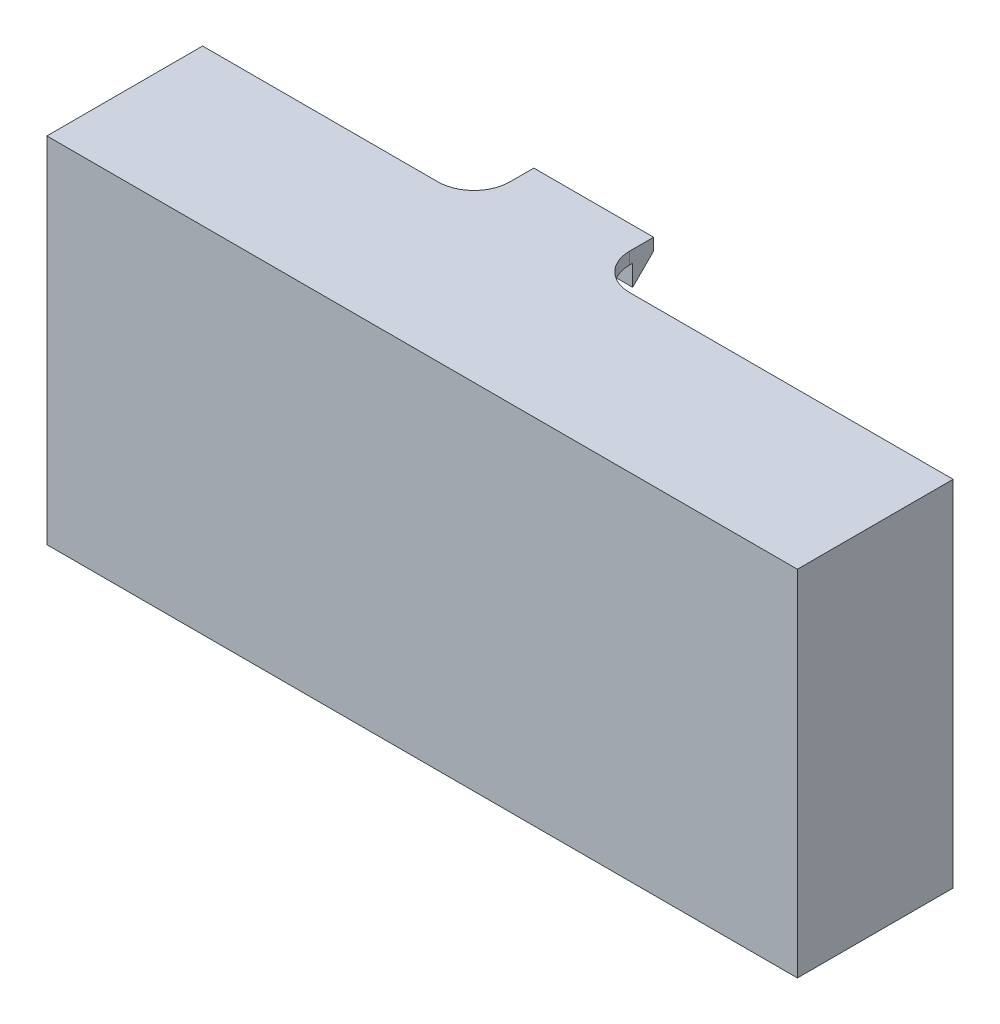
SolidWorks part; units mm, degrees
note: The reader was unsure of these and kept them because the rebuilt part matched: shared geometry of "Sketch13<2>".
ref_plane "Front Plane" through (0, 0, 0) normal (0, 0, 1) x (1, 0, 0)
ref_plane "Top Plane" through (0, 0, 0) normal (0, 1, 0) x (1, 0, 0)
ref_plane "Right Plane" through (0, 0, 0) normal (1, 0, 0) x (0, 0, -1)
sketch "Sketch1" plane through (0, 0, 0) normal (0, 0, 1) x (1, 0, 0)
  line L5 (1.25, -1.25) -> (1.25, 28.301)
  line L6 (1.25, 28.301) -> (-61.3972, 28.301)
  line L7 (-61.3972, 28.301) -> (-61.3972, -1.25)
  line L8 (-61.3972, -1.25) -> (1.25, -1.25)
  line L13 (0.25, -0.25) -> (0.25, 27.301)
  line L14 (0.25, 27.301) -> (-60.3972, 27.301)
  line L15 (-60.3972, 27.301) -> (-60.3972, -0.25)
  line L16 (-60.3972, -0.25) -> (0.25, -0.25)
  dimension "D2" = 1
extrude "Boss-Extrude1" add sketch "Sketch1" along normal blind 11
sketch "Sketch3" plane through (-61.3972, 0, 0) normal (-1, 0, 0) x (0, 0, 1)
  line L0 (0, 17.5514) -> (0.75, 18.3233)
  line L1 (0, 28.301) -> (0, -1.25) construction
  line L2 (0.75, 18.3233) -> (0.75, 24.3233)
  line L3 (0.75, 24.3233) -> (0, 25.0952)
  line L4 (0, 25.0952) -> (0, 17.5514)
  line L5 (0, 21.3233) -> (11, 21.3233) construction
  line L6 (11, 28.301) -> (11, -1.25) construction
  line L7 (-2.8448, 17.5514) -> (0, 17.5514) construction
  point P11 (0.75, 21.3233)
  dimension "D1" = 6
  dimension "D2" = 0.75
extrude "Cut-Extrude1" cut sketch "Sketch3" against normal up to next
sketch "Sketch4" plane through (0, -0.25, 0) normal (0, 1, 0) x (1, 0, 0)
  line L0 (0, -1.5875) -> (-60.1472, -1.5875) construction
  line L1 (-55.3972, -1.8375) -> (-53.3972, -1.8375)
  line L2 (-55.3972, -1.8375) -> (-55.3972, -2.8375)
  line L3 (-55.3972, -2.8375) -> (-53.3972, -2.8375)
  line L4 (-53.3972, -1.8375) -> (-53.3972, -2.8375)
  line L5 (-60.3972, -11) -> (-60.3972, 0) construction
  line L6 (-6.75, -1.8375) -> (-4.75, -1.8375)
  line L7 (-6.75, -1.8375) -> (-6.75, -2.8375)
  line L8 (-6.75, -2.8375) -> (-4.75, -2.8375)
  line L9 (-4.75, -1.8375) -> (-4.75, -2.8375)
  line L10 (0.25, -11) -> (0.25, 0) construction
  point P10 (-55.3972, -2.3375)
  dimension "D1" = 2
  dimension "D2" = 1
  dimension "D3" = 5
  dimension "D4" = 5
  dimension "D5" = 0.25
extrude "Boss-Extrude2" add sketch "Sketch4" along normal blind 1
sketch "Sketch6" plane through (0, 27.301, 0) normal (0, -1, 0) x (1, 0, 0)
  line L1 (-1.75, 1.8375) -> (-3.75, 1.8375)
  line L2 (-1.75, 1.8375) -> (-1.75, 2.8375)
  line L3 (-1.75, 2.8375) -> (-3.75, 2.8375)
  line L4 (-3.75, 1.8375) -> (-3.75, 2.8375)
  line L5 (-49.3776, 1.5875) -> (-49.3776, 6.2611) construction
  line L6 (-50.3776, 2.2832) -> (-52.3776, 2.2832)
  line L7 (-50.3776, 2.2832) -> (-50.3776, 3.2832)
  line L8 (-50.3776, 3.2832) -> (-52.3776, 3.2832)
  line L9 (-52.3776, 2.2832) -> (-52.3776, 3.2832)
  line L10 (0.25, 11) -> (0.25, 0) construction
  line L11 (-60.1472, 1.5875) -> (0, 1.5875) construction
  dimension "D1" = 1
  dimension "D2" = 2
  dimension "D3" = 1
  dimension "D4" = 2
  dimension "D5" = 0.25
extrude "Boss-Extrude3" add sketch "Sketch6" along normal blind 1
sketch "Sketch7" plane through (1.25, 0, 0) normal (1, 0, 0) x (0, 0, -1)
  line L1 (0, 27.951) -> (1, 27.951)
  line L3 (0, 27.301) -> (0, 25.0952) construction
  line L4 (0, 26.951) -> (0, 27.951)
  line L5 (0, 27.051) -> (-1.5875, 27.051) construction
  line L6 (1, 27.951) -> (1, 26.951)
  line L7 (1, 26.951) -> (0, 26.951)
  dimension "D1" = 1
  dimension "D2" = 1
  dimension "D3" = 0.1
extrude "Boss-Extrude4" add sketch "Sketch7" against normal blind 10 from offset 30 contours L4 L1 L6 L7 offset against normal yes
sketch "Sketch9" plane through (1.25, 0, 0) normal (-1, 0, 0) x (0, 0, 1)
  line L1 (0, -1.25) -> (-1, -1.25)
  line L2 (0, -1.25) -> (0, 0.25)
  line L3 (0, 0.25) -> (-1, 0.25)
  line L4 (-1, -1.25) -> (-1, 0.25)
  dimension "D1" = 1
  dimension "D2" = 1.5
extrude "Boss-Extrude5" add sketch "Sketch9" against normal blind 10 from offset 40
sketch "Sketch11" plane through (1.25, 0, 0) normal (1, 0, 0) x (0, 0, -1)
  line L1 (5, 28.301) -> (5, 27.301)
  line L5 (-11, 28.301) -> (0, 28.301) construction
  line L7 (5, 28.301) -> (0, 28.301)
  line L8 (0, 28.301) -> (0, 27.301)
  line L10 (0, 27.301) -> (3.25, 27.301)
  line L17 (0, -1.25) -> (5, -1.25)
  line L24 (3.25, -0.25) -> (0, -0.25)
  line L25 (0, -1.25) -> (0, -0.25)
  line L26 (3.25, 27.301) -> (3.25, 25.551)
  line L27 (3.25, 25.551) -> (5, 27.301)
  line L28 (3.25, -0.25) -> (3.25, 1.5)
  line L29 (3.25, 1.5) -> (5, -0.25)
  line L30 (5, -0.25) -> (5, -1.25)
  point P7 (3.25, 1.948)
  dimension "D1" = 3.25
  dimension "D2" = 1
  dimension "D3" = 5
  dimension "D4" = 45
  dimension "D5" = 45
extrude "Boss-Extrude7" add sketch "Sketch11" against normal blind 10 from offset 30 offset against normal yes
sketch "Sketch12" plane through (0, 0, 11) normal (0, 0, 1) x (1, 0, 0)
  line L1 (1.25, 28.301) -> (-61.3972, 28.301)
  line L2 (1.25, 28.301) -> (1.25, -1.25)
  line L3 (1.25, -1.25) -> (-61.3972, -1.25)
  line L4 (-61.3972, 28.301) -> (-61.3972, -1.25)
extrude "Boss-Extrude8" add sketch "Sketch12" along normal blind 2
sketch "Sketch13" plane through (0, -1.25, 0) normal (0, -1, 0) x (1, 0, 0)
  line L4 (-28.75, 0) -> (1.25, 0) construction
  line L5 (-25.75, 0) -> (-28.75, 0)
  line L6 (-28.75, 0) -> (-28.75, -3)
  line L11 (-41.75, 0) -> (-38.75, 0)
  line L12 (-38.75, 0) -> (-38.75, -3)
  line L13 (-61.3972, 0) -> (-38.75, 0) construction
  arc A0 (-28.75, -3) -> (-25.75, 0) centre (-25.75, -3) cw
  arc A1 (-38.75, -3) -> (-41.75, 0) centre (-41.75, -3) ccw
  point P2 (-28.75, -3.0822)
  point P8 (0, 0)
  point P12 (-28.75, 0)
  point P19 (0, 0)
  point P23 (0, 0)
  point P24 (-38.75, -5)
  point P25 (0, 0)
  point P26 (-38.75, -3.0822)
  dimension "D1" = 3
  dimension "D2" = 3
extrude "Boss-Extrude9" add sketch "Sketch13" against normal up to surface (1 mm away) up to face at (-33.75, -0.25, -2.125)
extrude "Boss-Extrude10" add sketch "Sketch13<2>" along normal up to surface (1 mm away) from surface
sketch "Sketch13<2>" plane through (0, -1.25, 0) normal (0, -1, 0) x (1, 0, 0) same geometry as "Sketch13"
